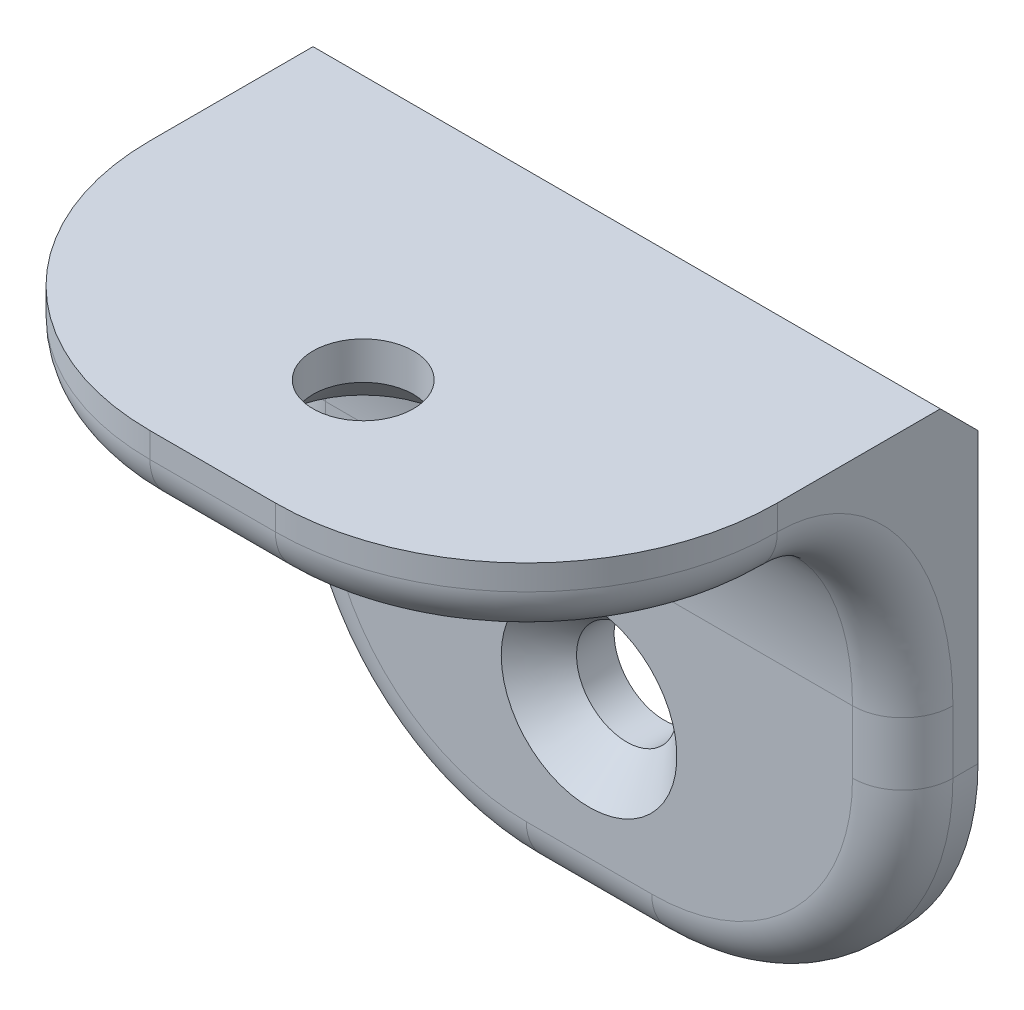
SolidWorks part; units mm, degrees
ref_plane "Front" through (0, 0, 0) normal (0, 0, 1) x (1, 0, 0)
ref_plane "Top" through (0, 0, 0) normal (0, 1, 0) x (1, 0, 0)
ref_plane "Right" through (0, 0, 0) normal (1, 0, 0) x (0, 0, -1)
sketch "Sketch1" plane through (0, 0, 0) normal (1, 0, 0) x (0, 0, -1)
  line L0 (0, 0) -> (0, 25.4)
  line L1 (0, 25.4) -> (-19.05, 25.4)
  line L2 (-19.05, 25.4) -> (-19.05, 29.21)
  line L3 (-19.05, 29.21) -> (3.81, 29.21)
  line L4 (3.81, 29.21) -> (3.81, 0)
  line L5 (3.81, 0) -> (0, 0)
  dimension "D1" = 3.81
  dimension "D2" = 25.4
  dimension "D3" = 19.05
extrude "Boss-Extrude1" add sketch "Sketch1" along normal blind 31.75
fillet "Fillet3" radius 12.7 4 edges at (31.75, 27.305, 19.05) (0, 27.305, 19.05) (31.75, 0, -1.905) (0, 0, -1.905)
fillet "Fillet1" radius 6.35 1 edges at (15.875, 25.4, 0) second distance 9.525 first distance on face at (15.875, 25.4, 9.3434)
fillet "Fillet2" radius 2.54 10 edges at (15.875, 0, 0) (15.875, 25.4, 19.05) (28.0303, 3.7197, 0) (3.7197, 3.7197, 0)
sketch "Sketch3" plane through (0, 0, 0) normal (0, 0, 1) x (1, 0, 0)
  line L0 (0, 9.2075) -> (15.875, 9.2075) construction
  line L1 (0, 15.875) -> (0, 2.54) construction
  line L2 (15.875, 9.2075) -> (15.875, 2.54) construction
  line L3 (12.7, 2.54) -> (19.05, 2.54) construction
  circle A0 centre (15.875, 9.2075) radius 2.54
  dimension "D1" = 5.08
extrude "Cut-Extrude1" cut sketch "Sketch3" against normal through all
sketch "Sketch4" plane through (0, 25.4, 0) normal (0, -1, 0) x (1, 0, 0)
  line L0 (15.875, 11.43) -> (15.875, 16.51) construction
  line L1 (19.05, 16.51) -> (12.7, 16.51) construction
  line L2 (15.875, 11.43) -> (0, 11.43) construction
  line L3 (0, 16.51) -> (0, 6.35) construction
  circle A0 centre (15.875, 11.43) radius 2.54
  dimension "D1" = 5.08
extrude "Cut-Extrude2" cut sketch "Sketch4" against normal through all
chamfer "Chamfer1" distance 1.905 angle 45 3 edges at (18.415, 9.2075, 0) (15.875, 25.4, 8.89) (15.875, 29.21, -3.81)
